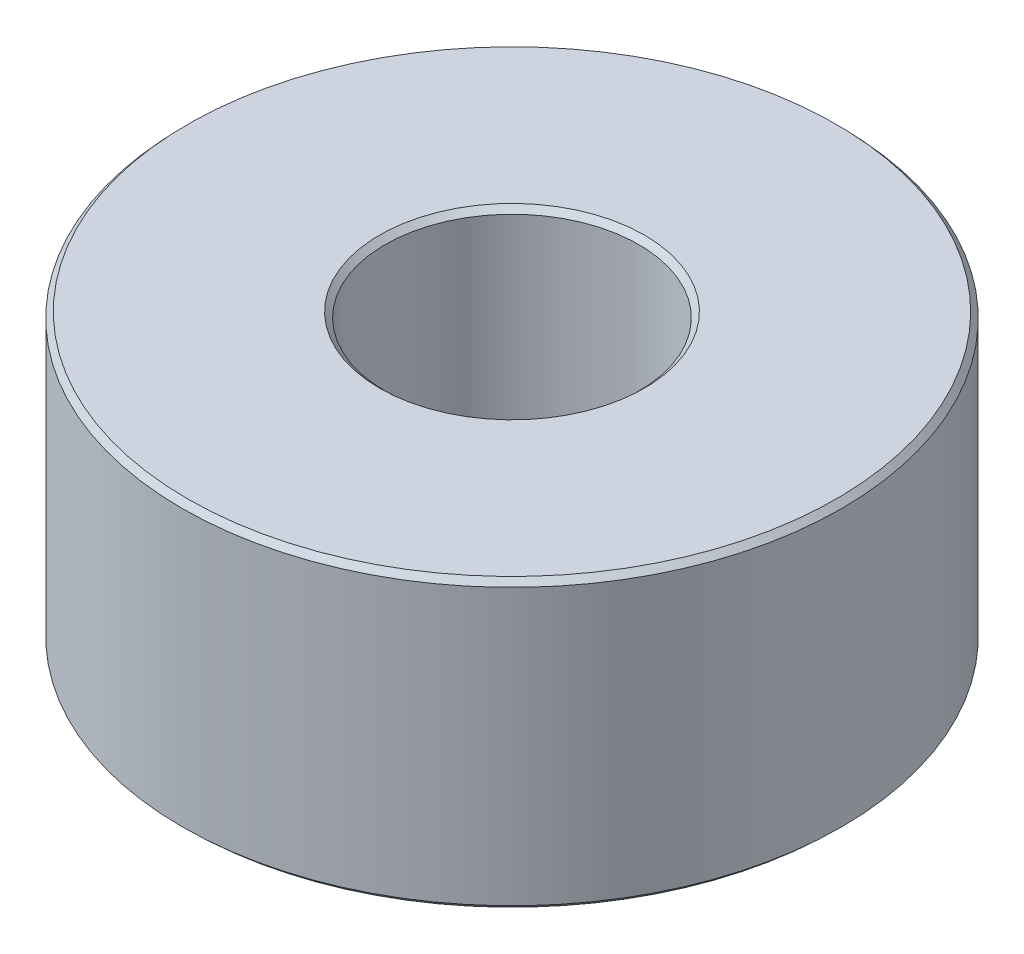
SolidWorks part; units mm, degrees
ref_plane "Front Plane" through (0, 0, 0) normal (0, 0, 1) x (1, 0, 0)
ref_plane "Top Plane" through (0, 0, 0) normal (0, 1, 0) x (1, 0, 0)
ref_plane "Right Plane" through (0, 0, 0) normal (1, 0, 0) x (0, 0, -1)
sketch "Sketch1" plane through (0, 0, 0) normal (0, 1, 0) x (1, 0, 0)
  circle A0 centre (0, 0) radius 42.5
  dimension "SLEEVE_OD" = 85
extrude "Boss-Extrude1" add sketch "Sketch1" along normal blind 36.9616
sketch "Sketch2" plane through (0, 0, 0) normal (0, 1, 0) x (1, 0, 0)
  circle A0 centre (0, 0) radius 16.3534
  dimension "BORE_D" = 32.7068
extrude "Cut-Extrude1" cut sketch "Sketch2" along normal through all
chamfer "Chamfer1" distance 0.7331 angle 43.213 4 edges at (0, 36.9616, 16.3534) (0, 0, 16.3534) (0, 0, 42.5) (0, 36.9616, 42.5) first distance on face at (0, 36.9616, 16.3534) first distance on face at (0, 0, 16.3534) first distance on face at (0, 36.9616, 42.5)
